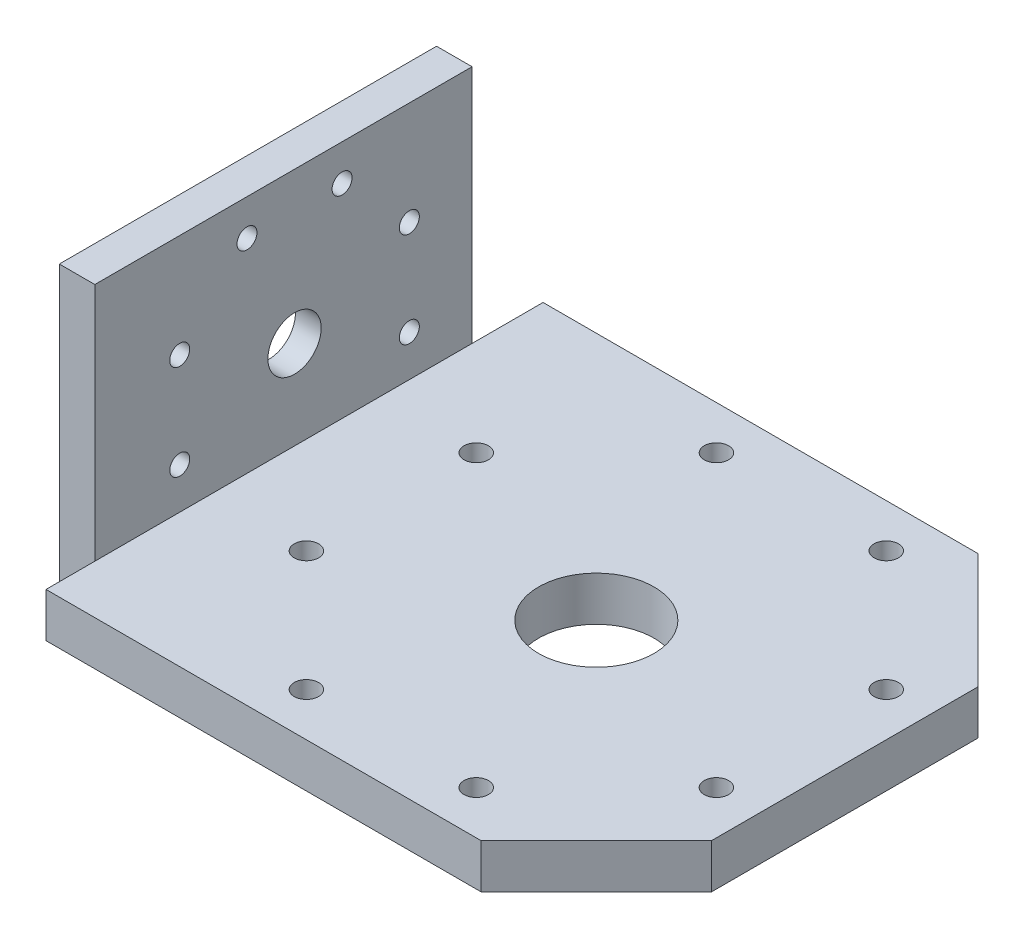
SolidWorks part; units mm, degrees
ref_plane "Front Plane" through (0, 0, 0) normal (0, 0, 1) x (1, 0, 0)
ref_plane "Top Plane" through (0, 0, 0) normal (0, 1, 0) x (1, 0, 0)
ref_plane "Right Plane" through (0, 0, 0) normal (1, 0, 0) x (0, 0, -1)
ref_plane "PL_Back_Plate_base" through (-76, 0, 0) normal (1, 0, 0) x (0, 0, -1)
sketch "SK_Back_Plate" plane through (-76, 0, 0) normal (1, 0, 0) x (0, 0, -1)
  line L0 (40, -36) -> (40, 34)
  line L1 (40, 34) -> (-45, 34)
  line L2 (-45, 34) -> (-45, -36)
  line L3 (-45, -36) -> (40, -36)
  circle A0 centre (25.8686, 10.7151) radius 2.25
  circle A1 centre (10.7151, 25.8686) radius 2.25
  circle A2 centre (-10.7151, 25.8686) radius 2.25
  circle A3 centre (-25.8686, 10.7151) radius 2.25
  circle A4 centre (-25.8686, -10.7151) radius 2.25
  circle A5 centre (-10.7151, -25.8686) radius 2.25
  circle A6 centre (10.7151, -25.8686) radius 2.25
  circle A7 centre (25.8686, -10.7151) radius 2.25
  circle A8 centre (0, 0) radius 6
  dimension "D9_SK_Back_Plate" = 4.5
  dimension "D12_SK_Back_Plate" = 4.5
  dimension "D15_SK_Back_Plate" = 4.5
  dimension "D18_SK_Back_Plate" = 4.5
  dimension "D21_SK_Back_Plate" = 4.5
  dimension "D24_SK_Back_Plate" = 4.5
  dimension "D27_SK_Back_Plate" = 4.5
  dimension "D30_SK_Back_Plate" = 4.5
  dimension "D33_SK_Back_Plate" = 12
  dimension "P1" = 40
  dimension "P2" = 36
  dimension "P3" = 40
  dimension "P4" = 34
  dimension "P5" = 45
  dimension "P6" = 34
  dimension "P7" = 45
  dimension "P8" = 36
  dimension "P10" = 25.8686
  dimension "P11" = 10.7151
  dimension "P13" = 10.7151
  dimension "P14" = 25.8686
  dimension "P16" = 10.7151
  dimension "P17" = 25.8686
  dimension "P19" = 25.8686
  dimension "P20" = 10.7151
  dimension "P22" = 25.8686
  dimension "P23" = 10.7151
  dimension "P25" = 10.7151
  dimension "P26" = 25.8686
  dimension "P28" = 10.7151
  dimension "P29" = 25.8686
  dimension "P31" = 25.8686
  dimension "P32" = 10.7151
extrude "Back_Plate" add sketch "SK_Back_Plate" along normal blind 8
ref_plane "PL_Roll_Pilot_Recess_base" through (-76, 0, 0) normal (1, 0, 0) x (0, 0, -1)
sketch "SK_Roll_Pilot_Recess" plane through (-76, 0, 0) normal (1, 0, 0) x (0, 0, -1)
  circle A0 centre (0, 0) radius 22.15
  dimension "D1_SK_Roll_Pilot_Recess" = 44.3
extrude "Roll_Pilot_Recess" cut sketch "SK_Roll_Pilot_Recess" along normal blind 2.2
ref_plane "PL_Medial_Plate_base" through (0, -30, 0) normal (0, 1, 0) x (1, 0, 0)
sketch "SK_Medial_Plate" plane through (0, -30, 0) normal (0, 1, 0) x (1, 0, 0)
  line L0 (-68, 56) -> (30, 56)
  line L1 (30, 56) -> (56, 30)
  line L2 (56, 30) -> (56, -30)
  line L3 (56, -30) -> (30, -56)
  line L4 (30, -56) -> (-68, -56)
  line L5 (-68, -56) -> (-68, 56)
  circle A0 centre (46.194, 19.1342) radius 2.75
  circle A1 centre (19.1342, 46.194) radius 2.75
  circle A2 centre (-19.1342, 46.194) radius 2.75
  circle A3 centre (-46.194, 19.1342) radius 2.75
  circle A4 centre (-46.194, -19.1342) radius 2.75
  circle A5 centre (-19.1342, -46.194) radius 2.75
  circle A6 centre (19.1342, -46.194) radius 2.75
  circle A7 centre (46.194, -19.1342) radius 2.75
  circle A8 centre (0, 0) radius 13
  dimension "D13_SK_Medial_Plate" = 5.5
  dimension "D16_SK_Medial_Plate" = 5.5
  dimension "D19_SK_Medial_Plate" = 5.5
  dimension "D22_SK_Medial_Plate" = 5.5
  dimension "D25_SK_Medial_Plate" = 5.5
  dimension "D28_SK_Medial_Plate" = 5.5
  dimension "D31_SK_Medial_Plate" = 5.5
  dimension "D34_SK_Medial_Plate" = 5.5
  dimension "D37_SK_Medial_Plate" = 26
  dimension "P1" = 68
  dimension "P2" = 56
  dimension "P3" = 30
  dimension "P4" = 56
  dimension "P5" = 56
  dimension "P6" = 30
  dimension "P7" = 56
  dimension "P8" = 30
  dimension "P9" = 30
  dimension "P10" = 56
  dimension "P11" = 68
  dimension "P12" = 56
  dimension "P14" = 46.194
  dimension "P15" = 19.1342
  dimension "P17" = 19.1342
  dimension "P18" = 46.194
  dimension "P20" = 19.1342
  dimension "P21" = 46.194
  dimension "P23" = 46.194
  dimension "P24" = 19.1342
  dimension "P26" = 46.194
  dimension "P27" = 19.1342
  dimension "P29" = 19.1342
  dimension "P30" = 46.194
  dimension "P32" = 19.1342
  dimension "P33" = 46.194
  dimension "P35" = 46.194
  dimension "P36" = 19.1342
extrude "Medial_Plate" add sketch "SK_Medial_Plate" along normal blind 10
equation "\"Roll_face_x\" = -76"
equation "\"Pitch_rear_y\" = -20"
equation "\"Plate_t\" = 10"
equation "\"Back_bottom_z\" = -40"
